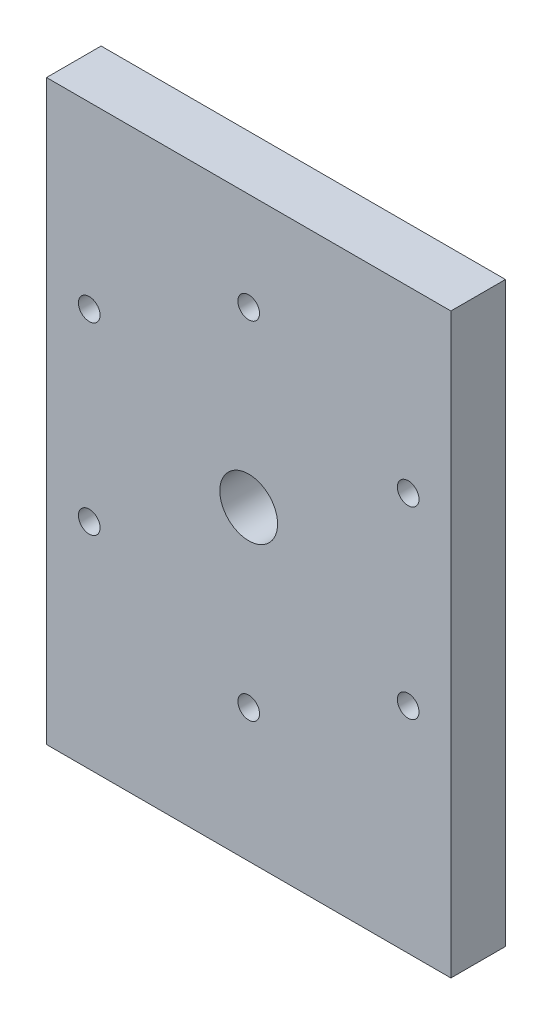
SolidWorks part; units mm, degrees
material "Acrylic (Medium-high impact)"
ref_plane "Front Plane" through (0, 0, 0) normal (0, 0, 1) x (1, 0, 0)
ref_plane "Top Plane" through (0, 0, 0) normal (0, 1, 0) x (1, 0, 0)
ref_plane "Right Plane" through (0, 0, 0) normal (1, 0, 0) x (0, 0, -1)
sketch "Sketch1" plane through (0, 0, 0) normal (0, 0, 1) x (1, 0, 0)
  line L0 (34.1802, 50.5429) -> (34.1802, 53.0508) construction
  line L1 (-44.45, 127) -> (44.45, 127)
  line L2 (-44.45, 127) -> (-44.45, 0)
  line L3 (-44.45, 0) -> (44.45, 0)
  line L4 (44.45, 127) -> (44.45, 0)
  circle A0 centre (0, 67.375) radius 6.35
  circle A7 centre (0, 67.375) radius 38.1 construction
  dimension "D1" = 127
  dimension "D3" = 12.7
  dimension "D12" = 76.2
  dimension "D2" = 88.9
  dimension "D5" = 67.375
extrude "Boss-Extrude1" add sketch "Sketch1" along normal blind 12
sketch "Sketch2" plane through (0, 0, 0) normal (0, 0, -1) x (-1, 0, 0)
  line L0 (0, 67.375) -> (-35.0578, 87.6156) construction
  line L1 (-32.9956, 48.325) -> (-32.9956, 86.425) construction
  line L2 (-32.9956, 86.425) -> (0, 105.475) construction
  line L3 (0, 105.475) -> (32.9956, 86.425) construction
  line L4 (32.9956, 86.425) -> (32.9956, 48.325) construction
  line L5 (32.9956, 48.325) -> (0, 29.275) construction
  line L6 (0, 29.275) -> (-32.9956, 48.325) construction
  line L7 (0, 67.375) -> (-35.0578, 47.1344) construction
  line L8 (0, 67.375) -> (35.0578, 47.1344) construction
  line L9 (0, 67.375) -> (35.0578, 87.6156) construction
  circle A3 centre (0, 67.375) radius 38.1 construction
  circle A5 centre (0, 105.475) radius 2.3812
  circle A6 centre (0, 29.275) radius 2.3813
  circle A7 centre (-35.0578, 87.6156) radius 2.3812
  circle A8 centre (-35.0578, 47.1344) radius 2.3812
  circle A9 centre (35.0578, 47.1344) radius 2.3812
  circle A10 centre (35.0578, 87.6156) radius 2.3812
  dimension "D1" = 76.2
  dimension "D2" = 4.7625
  dimension "D3" = 4.7625
extrude "Cut-Extrude1" cut sketch "Sketch2" against normal through all
sketch "Sketch3" plane through (0, 0, 0) normal (0, -1, 0) x (1, 0, 0)
  line L0 (31.75, 6) -> (-31.75, 6) construction
  line L2 (0, 0) -> (0, 12) construction
  line L3 (-44.45, 12) -> (44.45, 12) construction
  circle A0 centre (31.75, 6) radius 1.27
  circle A1 centre (0, 6) radius 1.27
  circle A2 centre (-31.75, 6) radius 1.27
  point P9 (0, 6)
  dimension "D2" = 2.54
  dimension "D1" = 31.75
extrude "Cut-Extrude2" cut sketch "Sketch3" against normal blind 12.7
hole_wizard "#10-32 Tapped Hole3" positions "Sketch11" profile "Sketch13" tap size "#10-32" standard "ANSI Inch"
sketch "Sketch11" plane through (0, 0, 0) normal (0, -1, 0) x (-1, 0, 0)
  point P0 (-31.75, -6)
  point P3 (0, -6)
  point P6 (31.75, -6)
sketch "Sketch13" plane through (31.75, 0, 6) normal (1, 0, 0) x (0, 0, -1)
  line L0 (0, 0) -> (0, 13.9133)
  line L1 (0, 13.9133) -> (2.0193, 12.7)
  line L2 (2.0193, 12.7) -> (2.0193, 0)
  line L5 (2.0193, 0) -> (0, 0)
  line L10 (0, 13.9133) -> (-2.0193, 12.7) construction
  line L11 (0, -6.35) -> (0, 107.95) construction
  dimension "Tap Drill Dia." = 4.0386
  dimension "Tap Drill Depth" = 12.7
  dimension "Drill Angle" = 118
cosmetic thread "Hole Thread11" parameters "D1"=10.16, "D2"=4.826
cosmetic thread "Hole Thread12" parameters "D1"=10.16, "D2"=4.826
cosmetic thread "Hole Thread13" parameters "D1"=10.16, "D2"=4.826
